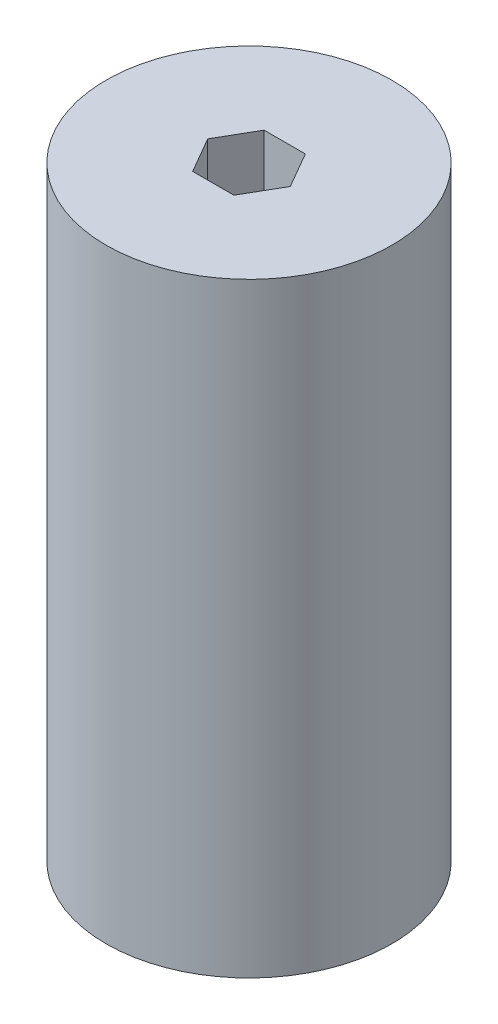
SolidWorks part; units mm, degrees
ref_plane "Front Plane" through (0, 0, 0) normal (0, 0, 1) x (1, 0, 0)
ref_plane "Top Plane" through (0, 0, 0) normal (0, 1, 0) x (1, 0, 0)
ref_plane "Right Plane" through (0, 0, 0) normal (1, 0, 0) x (0, 0, -1)
sketch "Sketch1" plane through (0, 0, 0) normal (0, 1, 0) x (1, 0, 0)
  line L1 (8.6603, 0) -> (4.3301, 7.5)
  line L2 (4.3301, 7.5) -> (-4.3301, 7.5)
  line L3 (-4.3301, 7.5) -> (-8.6603, 0)
  line L4 (-8.6603, 0) -> (-4.3301, -7.5)
  line L5 (-4.3301, -7.5) -> (4.3301, -7.5)
  line L6 (4.3301, -7.5) -> (8.6603, 0)
  circle A0 centre (0, 0) radius 7.5 construction
  circle A1 centre (0, 0) radius 30
  dimension "D1" = 60
  dimension "D2" = 15
extrude "Boss-Extrude1" add sketch "Sketch1" along normal blind 127
